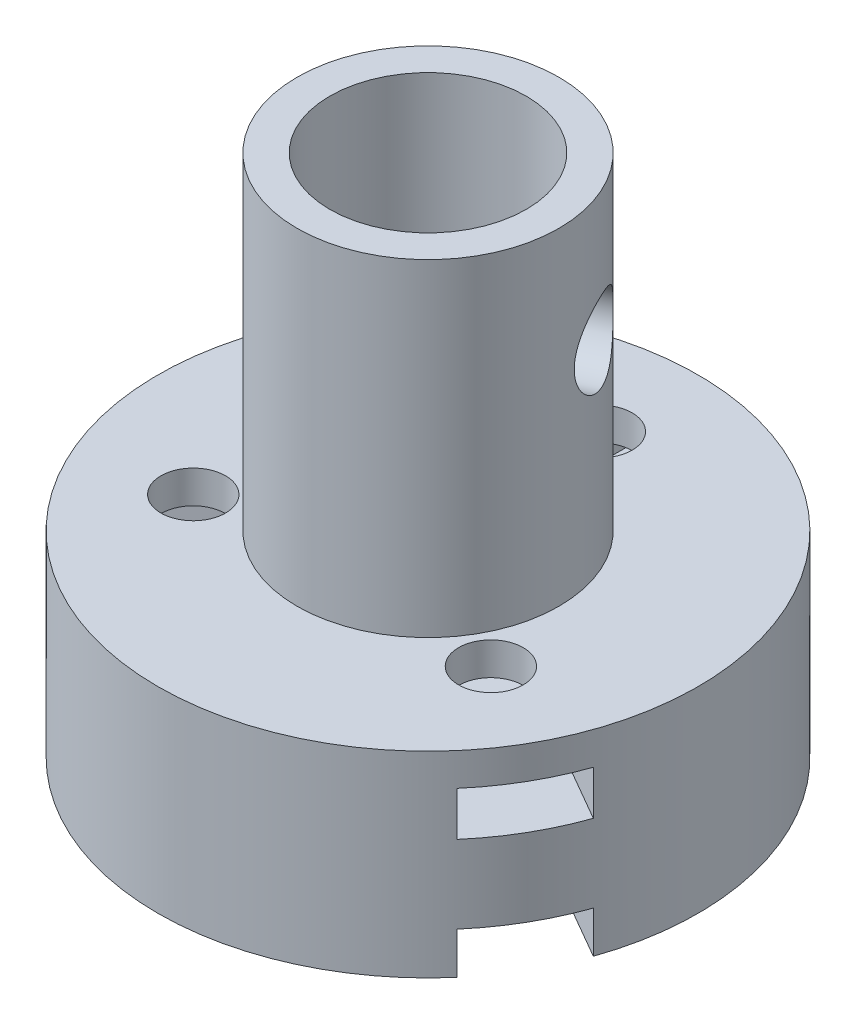
SolidWorks part; units mm, degrees
ref_plane "Alzado" through (0, 0, 0) normal (0, 0, 1) x (1, 0, 0)
ref_plane "Planta" through (0, 0, 0) normal (0, 1, 0) x (1, 0, 0)
ref_plane "Vista lateral" through (0, 0, 0) normal (1, 0, 0) x (0, 0, -1)
sketch "Croquis1" plane through (0, 0, 0) normal (0, 1, 0) x (1, 0, 0)
  circle A0 centre (0, 0) radius 16.5
  dimension "D1" = 33
extrude "Saliente-Extruir1" add sketch "Croquis1" along normal blind 12
sketch "Croquis2" plane through (0, 0, 0) normal (0, -1, 0) x (1, 0, 0)
  line L0 (-12.7644, 10.8914) -> (-15.8144, 5.6086)
  line L1 (-3.05, -16.5) -> (3.05, -16.5)
  line L2 (-3.05, -16.5) -> (-3.05, -4.5)
  line L3 (-3.05, -4.5) -> (3.05, -4.5)
  line L4 (3.05, -16.5) -> (3.05, -4.5)
  line L5 (-12.7644, 10.8914) -> (-2.3721, 4.8914)
  line L6 (-2.3721, 4.8914) -> (-5.4221, -0.3914)
  line L7 (-15.8144, 5.6086) -> (-5.4221, -0.3914)
  line L8 (15.8144, 5.6086) -> (12.7644, 10.8914)
  line L9 (15.8144, 5.6086) -> (5.4221, -0.3914)
  line L10 (5.4221, -0.3914) -> (2.3721, 4.8914)
  line L11 (12.7644, 10.8914) -> (2.3721, 4.8914)
  line L12 (0, -10.5) -> (0, 0) construction
  line L13 (0, 0) -> (9.0933, 5.25) construction
  circle A0 centre (0, 0) radius 16.5 construction
  circle A1 centre (0, 0) radius 16.5 construction
  circle A2 centre (0, -10.5) radius 1.975
  circle A3 centre (-9.0933, 5.25) radius 1.975
  circle A4 centre (9.0933, 5.25) radius 1.975
  point P5 (0, -16.5)
  point P11 (0, -4.5)
  point P25 (0, 0)
  dimension "D4" = 3.95
  dimension "D1" = 12
  dimension "D2" = 6.1
  dimension "D3" = 6
  dimension "D6" = 120
  dimension "D5" = 3
extrude "Cortar-Extruir1" cut sketch "Croquis2" against normal blind 2.55
extrude "Cortar-Extruir2" cut sketch "Croquis2<2>" against normal through all contours A2 | A3 | A4 region at (0, 0, -10.5)
sketch "Croquis2<2>" plane through (0, 0, 0) normal (0, -1, 0) x (1, 0, 0) same geometry as "Croquis2"
ref_plane "Plano1" through (0, 10, 0) normal (0, 1, 0) x (1, 0, 0)
sketch "Croquis3" plane through (0, 10, 0) normal (0, 1, 0) x (1, 0, 0)
  line L4 (3.05, 16.5) -> (-3.05, 16.5)
  line L5 (3.05, 4.5) -> (3.05, 16.5)
  line L6 (-3.05, 4.5) -> (3.05, 4.5)
  line L7 (-3.05, 16.5) -> (-3.05, 4.5)
  line L8 (3.05, 16.5) -> (-3.05, 16.5)
  line L9 (3.05, 4.5) -> (3.05, 16.5)
  line L10 (-3.05, 4.5) -> (3.05, 4.5)
  line L11 (-3.05, 16.5) -> (-3.05, 4.5)
  line L12 (12.7644, -10.8914) -> (15.8144, -5.6086)
  line L13 (2.3721, -4.8914) -> (12.7644, -10.8914)
  line L14 (5.4221, 0.3914) -> (2.3721, -4.8914)
  line L15 (15.8144, -5.6086) -> (5.4221, 0.3914)
  line L16 (12.7644, -10.8914) -> (15.8144, -5.6086)
  line L17 (2.3721, -4.8914) -> (12.7644, -10.8914)
  line L18 (5.4221, 0.3914) -> (2.3721, -4.8914)
  line L19 (15.8144, -5.6086) -> (5.4221, 0.3914)
  line L20 (-15.8144, -5.6086) -> (-12.7644, -10.8914)
  line L21 (-12.7644, -10.8914) -> (-2.3721, -4.8914)
  line L22 (-2.3721, -4.8914) -> (-5.4221, 0.3914)
  line L23 (-5.4221, 0.3914) -> (-15.8144, -5.6086)
  line L24 (-15.8144, -5.6086) -> (-12.7644, -10.8914)
  line L25 (-12.7644, -10.8914) -> (-2.3721, -4.8914)
  line L26 (-2.3721, -4.8914) -> (-5.4221, 0.3914)
  line L27 (-5.4221, 0.3914) -> (-15.8144, -5.6086)
  circle A1 centre (0, 10.5) radius 1.975
  circle A2 centre (0, 10.5) radius 1.975
  circle A3 centre (9.0933, -5.25) radius 1.975
  circle A4 centre (9.0933, -5.25) radius 1.975
  circle A5 centre (-9.0933, -5.25) radius 1.975
  circle A6 centre (-9.0933, -5.25) radius 1.975
  dimension "D1" = 0
  dimension "D2" = 0
  dimension "D3" = 0
  dimension "D4" = 0
  dimension "D5" = 0
  dimension "D6" = 0
extrude "Cortar-Extruir3" cut sketch "Croquis3" against normal blind 2.7
sketch "Croquis4" plane through (0, 12, 0) normal (0, 1, 0) x (1, 0, 0)
  circle A0 centre (0, 0) radius 6
  dimension "D1" = 12
extrude "Extruir-Lámina1" add sketch "Croquis4" along normal blind 20 thin thin type one direction wall 2
ref_plane "Plano2" through (7.2505, 0, -3.3809) normal (0.9063, 0, -0.4226) x (0, -1, 0)
sketch "Croquis5" plane through (7.2505, 0, -3.3809) normal (0.9063, 0, -0.4226) x (0, -1, 0)
  line L0 (-32, 8) -> (-32, -8) construction
  circle A0 centre (-24, 0) radius 2.45
  point P2 (0, 0)
  dimension "D1" = 4.9
  dimension "D2" = 8
extrude "Cortar-Extruir4" cut sketch "Croquis5" against normal up to next contours A0
